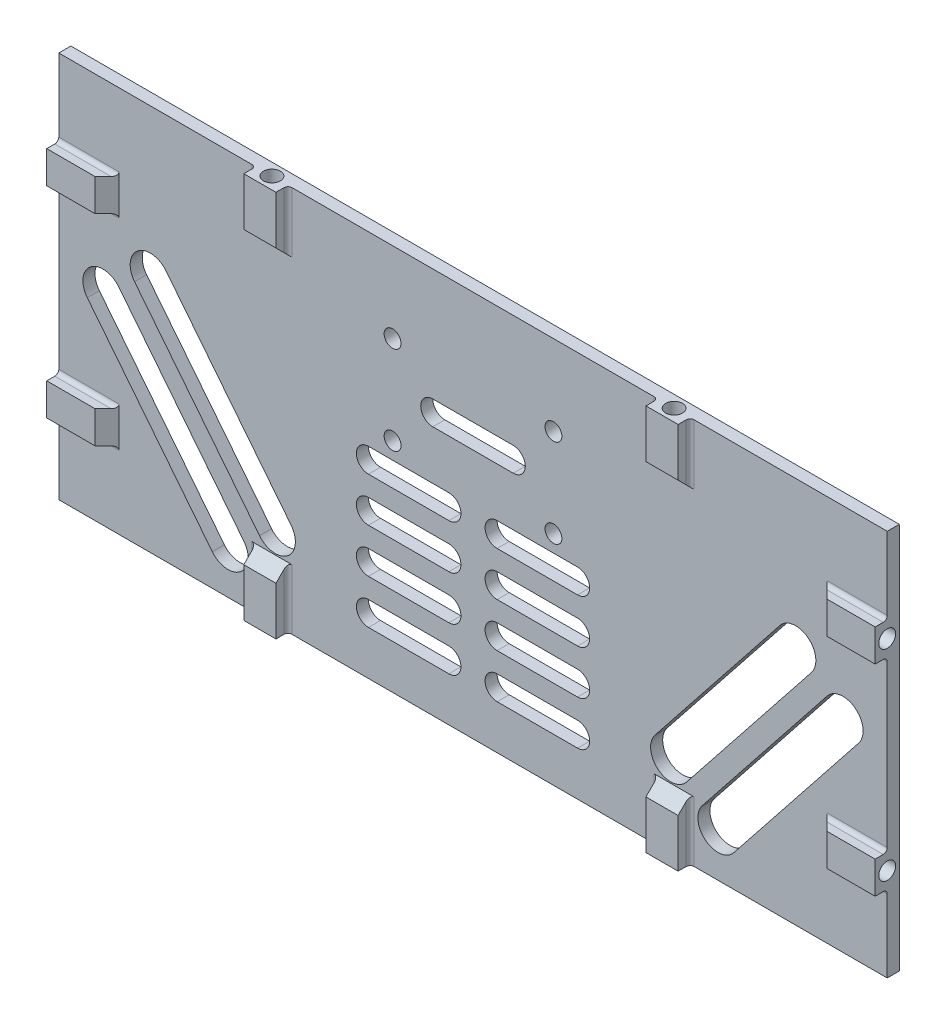
SolidWorks part; units mm, degrees
ref_plane "Front Plane" through (0, 0, 0) normal (1, 0, 0) x (0, 1, 0)
ref_plane "Top Plane" through (0, 0, 0) normal (0, 0, 1) x (0, 1, 0)
ref_plane "Right Plane" through (0, 0, 0) normal (0, 1, 0) x (-1, 0, 0)
sketch "Sketch1" plane through (0, 0, 0) normal (0, 0, 1) x (0, 1, 0)
  line L0 (11, 163.9146) -> (50.1625, 195) construction
  line L1 (0, 0) -> (96.2019, 0)
  line L2 (0, 0) -> (0, 206)
  line L3 (0, 206) -> (96.2019, 206)
  line L4 (96.2019, 0) -> (96.2019, 206)
  line L5 (7.8915, 167.8308) -> (47.0539, 198.9162)
  line L6 (14.1085, 159.9983) -> (53.271, 191.0838)
  line L7 (20.3256, 152.1659) -> (59.4881, 183.2513) construction
  line L8 (17.2171, 156.0821) -> (56.3795, 187.1675)
  line L9 (23.4342, 148.2496) -> (62.5966, 179.335)
  line L10 (20.3256, 53.8341) -> (59.4881, 22.7487) construction
  line L11 (23.4342, 57.7504) -> (62.5966, 26.665)
  line L12 (17.2171, 49.9179) -> (56.3795, 18.8325)
  line L13 (11, 42.0854) -> (50.1625, 11) construction
  line L14 (14.1085, 46.0017) -> (53.271, 14.9162)
  line L15 (7.8915, 38.1692) -> (47.0539, 7.0838)
  line L16 (6, 200) -> (90.2019, 200) construction
  line L17 (90.2019, 6) -> (90.2019, 200) construction
  line L18 (6, 6) -> (90.2019, 6) construction
  line L19 (6, 6) -> (6, 200) construction
  line L20 (55.8833, 147.5809) -> (78.9144, 118.5655) construction
  line L21 (65.5213, 70.5614) -> (46.6427, 46.7775) construction
  line L22 (96.2019, 103) -> (0, 103) construction
  line L23 (14, 129) -> (14, 109) construction
  line L24 (17, 129) -> (17, 109)
  line L25 (11, 129) -> (11, 109)
  line L26 (25, 129) -> (25, 109) construction
  line L27 (28, 129) -> (28, 109)
  line L28 (22, 129) -> (22, 109)
  line L29 (36, 129) -> (36, 109) construction
  line L30 (39, 129) -> (39, 109)
  line L31 (33, 129) -> (33, 109)
  line L32 (47, 129) -> (47, 109) construction
  line L33 (50, 129) -> (50, 109)
  line L34 (44, 129) -> (44, 109)
  line L41 (14, 77) -> (14, 97) construction
  line L42 (17, 77) -> (17, 97)
  line L43 (11, 77) -> (11, 97)
  line L44 (25, 77) -> (25, 97) construction
  line L45 (28, 77) -> (28, 97)
  line L46 (22, 77) -> (22, 97)
  line L47 (36, 77) -> (36, 97) construction
  line L48 (39, 77) -> (39, 97)
  line L49 (33, 77) -> (33, 97)
  line L50 (47, 77) -> (47, 97) construction
  line L51 (50, 77) -> (50, 97)
  line L52 (44, 77) -> (44, 97)
  line L53 (54.2019, 83) -> (76.2019, 83) construction
  line L56 (54.2019, 83) -> (54.2019, 123) construction
  line L59 (65.2019, 113) -> (65.2019, 93) construction
  line L60 (68.2019, 113) -> (68.2019, 93)
  line L61 (62.2019, 113) -> (62.2019, 93)
  line L67 (54.2019, 123) -> (76.2019, 123) construction
  line L68 (76.2019, 83) -> (76.2019, 123) construction
  line L69 (54.2019, 83) -> (76.2019, 123) construction
  line L70 (54.2019, 123) -> (76.2019, 83) construction
  line L287 (69, 129) -> (69, 109) construction
  line L288 (72, 129) -> (72, 109)
  line L289 (66, 129) -> (66, 109)
  line L290 (58, 129) -> (58, 109) construction
  line L291 (61, 129) -> (61, 109)
  line L292 (55, 129) -> (55, 109)
  line L293 (69, 129) -> (69, 109) construction
  line L294 (72, 129) -> (72, 109)
  line L295 (66, 129) -> (66, 109)
  line L296 (58, 129) -> (58, 109) construction
  line L297 (61, 129) -> (61, 109)
  line L298 (55, 129) -> (55, 109)
  arc A0 (7.8915, 167.8308) -> (14.1085, 159.9983) centre (11, 163.9146) ccw
  arc A1 (53.271, 191.0838) -> (47.0539, 198.9162) centre (50.1625, 195) ccw
  arc A2 (17.2171, 156.0821) -> (23.4342, 148.2496) centre (20.3256, 152.1659) ccw
  arc A3 (62.5966, 179.335) -> (56.3795, 187.1675) centre (59.4881, 183.2513) ccw
  arc A4 (23.4342, 57.7504) -> (17.2171, 49.9179) centre (20.3256, 53.8341) ccw
  arc A5 (56.3795, 18.8325) -> (62.5966, 26.665) centre (59.4881, 22.7487) ccw
  arc A6 (14.1085, 46.0017) -> (7.8915, 38.1692) centre (11, 42.0854) ccw
  arc A7 (47.0539, 7.0838) -> (53.271, 14.9162) centre (50.1625, 11) ccw
  circle A9 centre (76.2019, 123) radius 2.1
  circle A11 centre (76.2019, 83) radius 2.1
  arc A12 (17, 129) -> (11, 129) centre (14, 129) ccw
  arc A13 (11, 109) -> (17, 109) centre (14, 109) ccw
  arc A14 (28, 129) -> (22, 129) centre (25, 129) ccw
  arc A15 (22, 109) -> (28, 109) centre (25, 109) ccw
  arc A16 (39, 129) -> (33, 129) centre (36, 129) ccw
  arc A17 (33, 109) -> (39, 109) centre (36, 109) ccw
  arc A18 (50, 129) -> (44, 129) centre (47, 129) ccw
  arc A19 (44, 109) -> (50, 109) centre (47, 109) ccw
  arc A24 (17, 77) -> (11, 77) centre (14, 77) cw
  arc A25 (11, 97) -> (17, 97) centre (14, 97) cw
  arc A26 (28, 77) -> (22, 77) centre (25, 77) cw
  arc A27 (22, 97) -> (28, 97) centre (25, 97) cw
  arc A28 (39, 77) -> (33, 77) centre (36, 77) cw
  arc A29 (33, 97) -> (39, 97) centre (36, 97) cw
  arc A30 (50, 77) -> (44, 77) centre (47, 77) cw
  arc A31 (44, 97) -> (50, 97) centre (47, 97) cw
  arc A36 (68.2019, 113) -> (62.2019, 113) centre (65.2019, 113) ccw
  arc A37 (62.2019, 93) -> (68.2019, 93) centre (65.2019, 93) ccw
  circle A42 centre (54.2019, 123) radius 2.1
  circle A43 centre (54.2019, 83) radius 2.1
  arc A192 (72, 129) -> (66, 129) centre (69, 129) ccw
  arc A193 (66, 109) -> (72, 109) centre (69, 109) ccw
  arc A194 (61, 129) -> (55, 129) centre (58, 129) ccw
  arc A195 (55, 109) -> (61, 109) centre (58, 109) ccw
  point P7 (30.5812, 179.4573)
  point P12 (39.9068, 167.7086)
  point P19 (39.9068, 38.2914)
  point P26 (30.5812, 26.5427)
  point P40 (65.2019, 103)
  point P42 (65.2019, 103)
  point P54 (14, 119)
  point P59 (65.2019, 103)
  point P63 (25, 119)
  point P70 (36, 119)
  point P77 (47, 119)
  point P84 (69, 119)
  point P94 (91.2696, 103)
  point P97 (14, 87)
  point P104 (25, 87)
  point P111 (36, 87)
  point P118 (47, 87)
  point P146 (58, 119)
  point P153 (69, 119)
  point P160 (58, 119)
  point P167 (69, 119)
  point P174 (58, 119)
  point P181 (69, 119)
  point P188 (58, 119)
  point P195 (69, 119)
  point P202 (58, 119)
  point P209 (69, 119)
  point P216 (58, 119)
  point P223 (69, 119)
  point P230 (58, 119)
  point P237 (69, 119)
  point P244 (58, 119)
  point P251 (69, 119)
  point P258 (58, 119)
  point P265 (69, 119)
  point P272 (58, 119)
  point P279 (69, 119)
  point P286 (58, 119)
  point P293 (69, 119)
  point P300 (58, 119)
  point P307 (69, 119)
  point P314 (58, 119)
  point P321 (69, 119)
  point P328 (58, 119)
  point P335 (69, 119)
  point P342 (58, 119)
  point P349 (69, 119)
  point P356 (58, 119)
  point P363 (69, 119)
  point P370 (58, 119)
  point P377 (69, 119)
  point P384 (58, 119)
  point P391 (69, 119)
  point P398 (58, 119)
  point P405 (69, 119)
  point P412 (58, 119)
  point P419 (69, 119)
  point P426 (58, 119)
  point P433 (69, 119)
  point P440 (58, 119)
  point P447 (69, 119)
  point P454 (58, 119)
  point P461 (69, 119)
  point P468 (58, 119)
  point P475 (69, 119)
  point P482 (58, 119)
  point P489 (69, 119)
  point P496 (58, 119)
  point P503 (69, 119)
  point P510 (58, 119)
  point P517 (69, 119)
  point P524 (58, 119)
  point P531 (69, 119)
  point P538 (58, 119)
  point P545 (69, 119)
  point P552 (58, 119)
  point P559 (69, 66)
  point P566 (58, 66)
  point P573 (69, 66)
  point P580 (58, 66)
  point P587 (69, 56)
  point P594 (58, 56)
  point P601 (69, 56)
  point P608 (58, 56)
  point P615 (69, 119)
  point P622 (58, 119)
  point P629 (69, 119)
  point P636 (58, 119)
  point P643 (69, 119)
  point P650 (58, 119)
  point P657 (69, 119)
  point P664 (58, 119)
  point P671 (69, 119)
  point P678 (58, 119)
  dimension "D9" = 4.2
  dimension "D1" = 96.2019
  dimension "D2" = 206
  dimension "D4" = 5
  dimension "D5" = 5
  dimension "D6" = 103.118
  dimension "D7" = 10
  dimension "D8" = 50
  dimension "D10" = 20
  dimension "D11" = 20
  dimension "D14" = 5
  dimension "D15" = 5
  dimension "D16" = 6
  dimension "20" = 20
  dimension "D17" = 6
  dimension "D18" = 20
  dimension "D19" = 6
  dimension "D12" = 22
  dimension "D3" = 6
  dimension "D13" = 6
extrude "Boss-Extrude1" add sketch "Sketch1" along normal blind 3
sketch "Sketch2" plane through (0, 0, 0) normal (0, -1, 0) x (1, 0, 0)
  line L0 (-153, 6) -> (-153, 0) construction
  line L1 (-157, 6) -> (-149, 6)
  line L2 (-53, 6) -> (-53, 0) construction
  line L5 (-103, 3) -> (-103, 0) construction
  line L6 (-206, 3) -> (0, 3) construction
  line L7 (-206, 0) -> (0, 0) construction
  line L8 (-157, 6) -> (-157, 0)
  line L9 (-157, 0) -> (-149, 0)
  line L10 (-149, 6) -> (-149, 0)
  line L11 (-57, 6) -> (-57, 0)
  line L12 (-49, 0) -> (-57, 0)
  line L13 (-49, 6) -> (-49, 0)
  line L14 (-49, 6) -> (-57, 6)
  circle A0 centre (-153, 3) radius 2.1
  circle A2 centre (-53, 3) radius 2.1
  dimension "D3" = 6
  dimension "D1" = 4.2
  dimension "D4" = 8
  dimension "D2" = 50
extrude "Boss-Extrude2" add sketch "Sketch2<3>" against normal blind 12 contours L8 L9 L10 L1 | L14 L11 L12 L13
sketch "Sketch2<3>" plane through (0, 0, 0) normal (0, -1, 0) x (1, 0, 0) same geometry as "Sketch2"
extrude "Boss-Extrude3" add sketch "Sketch2<4>" along normal blind 12 from surface contours L14 L11 L12 L13 | L1 L10 L9 L8 starting at face at (-103, 96.2019, 1.5)
sketch "Sketch2<4>" plane through (0, 0, 0) normal (0, -1, 0) x (1, 0, 0) same geometry as "Sketch2"
sketch "Sketch3" plane through (0, 0, 0) normal (1, 0, 0) x (0, 1, 0)
  line L1 (23.1009, 6) -> (23.1009, 0) construction
  line L4 (0, 3) -> (96.2019, 3) construction
  line L5 (48.1009, 3) -> (48.1009, 0) construction
  line L6 (0, 0) -> (96.2019, 0) construction
  line L7 (19.1009, 0) -> (27.1009, 0)
  line L8 (19.1009, 0) -> (19.1009, 6)
  line L9 (19.1009, 6) -> (27.1009, 6)
  line L10 (27.1009, 0) -> (27.1009, 6)
  line L11 (77.1009, 0) -> (69.1009, 0)
  line L12 (69.1009, 0) -> (69.1009, 6)
  line L13 (77.1009, 6) -> (69.1009, 6)
  line L14 (77.1009, 0) -> (77.1009, 6)
  circle A0 centre (23.1009, 3) radius 2.1
  circle A2 centre (73.1009, 3) radius 2.1
  dimension "D3" = 6
  dimension "D1" = 4.2
  dimension "D4" = 8
  dimension "D2" = 25
extrude "Boss-Extrude4" add sketch "Sketch3<3>" against normal blind 12 contours L9 L10 L7 L8 | L13 L12 L11 L14
sketch "Sketch3<3>" plane through (0, 0, 0) normal (1, 0, 0) x (0, 1, 0) same geometry as "Sketch3"
extrude "Boss-Extrude5" add sketch "Sketch3<4>" along normal blind 12 from surface contours L9 L10 L7 L8 | L13 L12 L11 L14 starting at face at (-206, 48.1009, 1.5)
sketch "Sketch3<4>" plane through (0, 0, 0) normal (1, 0, 0) x (0, 1, 0) same geometry as "Sketch3"
extrude "Cut-Extrude1" cut sketch "Sketch2" against normal blind 10 contours A2 | A0
extrude "Cut-Extrude2" cut sketch "Sketch2<2>" along normal blind 10 from surface contours A2 | A0 starting at face at (-103, 96.2019, 3.5)
sketch "Sketch2<2>" plane through (0, 0, 0) normal (0, -1, 0) x (1, 0, 0) same geometry as "Sketch2"
extrude "Cut-Extrude3" cut sketch "Sketch3" against normal blind 10 contours A2 | A0
extrude "Cut-Extrude4" cut sketch "Sketch3<2>" along normal blind 10 from surface contours A2 | A0 starting at face at (-206, 48.1009, 3.5)
sketch "Sketch3<2>" plane through (0, 0, 0) normal (1, 0, 0) x (0, 1, 0) same geometry as "Sketch3"
chamfer "Chamfer1" distance 3 angle 45 8 edges at (-53, 84.2019, 3) (-153, 84.2019, 3) (-194, 73.1009, 3) (-194, 23.1009, 3) (-153, 12, 3) (-53, 12, 3) (-12, 23.1009, 3) (-12, 73.1009, 3)
fillet "Fillet1" radius 1 16 edges at (-149, 7.5, 3) (-157, 7.5, 3) (-198.5, 27.1009, 3) (-198.5, 19.1009, 3) (-198.5, 69.1009, 3) (-198.5, 77.1009, 3) (-157, 88.7019, 3) (-149, 88.7019, 3) (-7.5, 69.1009, 3) (-49, 88.7019, 3) (-57, 88.7019, 3) (-7.5, 77.1009, 3) (-57, 7.5, 3) (-49, 7.5, 3) (-7.5, 27.1009, 3) (-7.5, 19.1009, 3)
equation "\"MotorDriverLength\"= 60mm"
equation "\"MotorLength\"= 60"
equation "\"MotorDriverWidth\"=44"
equation "\"MotorWidth\"= 37"
equation "\"InnerWallThickness\"=3"
equation "\"BatteryWidth\"= 60"
equation "\"OuterWallThickness\" = 6"
equation "\"CompartmentHeight\"=37"
equation "\"CompartmentWidth\"= \"MotorDriverLength\""
equation "\"MotorDiameter\"=37"
equation "\"BatteryHeight\"=24.2019"
equation "\"MotorDriverHeight\"=28"
equation "\"CircuitHeight\"=30"
equation "\"FanThickness\"= 10"
equation "\"FanHeight\"=50"
equation "\"MotorShaftHole\"=12"
equation "\"BearingBore\"=10"
equation "\"MinShinWidth\"= 20"
equation "\"ShinThickness\"=10"
equation "\"PivotDistance\"=30"
equation "\"ThighLength\"= 150"
equation "\"KneeLength\" =80"
equation "\"HipBore\"=27"
equation "\"ThighThickness\"=10"
equation "\"MaxBending\"=135"
equation "\"MaxStretchingAngle\"= 50"
equation "\"ThighJointDistance\"=157.485"
equation "\"ShinLength\"=120"
equation "\"BearingDiameter\"= 10"
equation "\"CircuitLength\"=50"
equation "\"ChessisInnerWidth\"= \"OuterWallThickness\" * 2 + \"MotorDriverLength\" + \"MotorDiameter\" + \"InnerWallThickness\" * 3 + \"CircuitLength\""
equation "\"ChessisHeight\"= \"BatteryHeight\" + 10 + \"InnerWallThickness\" + \"MotorDiameter\" + 10 + \"OuterWallThickness\" * 2"
equation "\"D1@Sketch1\"=\"ChessisHeight\""
equation "\"ChassisWidth\"= \"MotorDriverWidth\"*4+30"
equation "\"D2@Sketch1\"=\"ChassisWidth\""
equation "\"D1@Boss-Extrude1\"=\"OuterWallThickness\""
equation "\"D3@Sketch2\"=\"OuterWallThickness\""
equation "\"D3@Sketch3\"=\"OuterWallThickness\""
